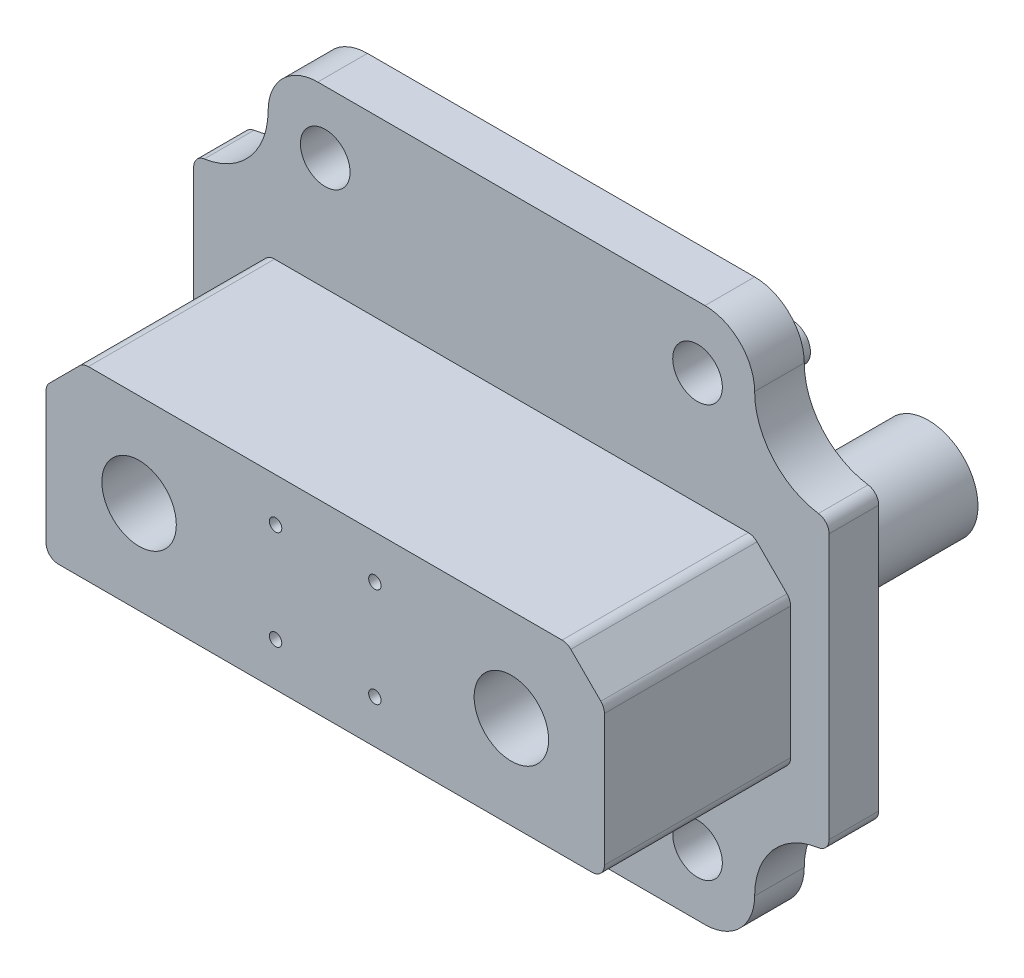
SolidWorks part; units mm, degrees
ref_plane "前视基准面" through (0, 0, 0) normal (0, 0, 1) x (1, 0, 0)
ref_plane "上视基准面" through (0, 0, 0) normal (0, 1, 0) x (1, 0, 0)
ref_plane "右视基准面" through (0, 0, 0) normal (1, 0, 0) x (0, 0, -1)
sketch "草图1" plane through (0, 0, 0) normal (0, 0, 1) x (1, 0, 0)
  line L0 (-6.4155, 0) -> (7.9227, 0) construction
  line L1 (0, -7.8725) -> (0, 7.2232) construction
  line L2 (0, 10.8) -> (-9.8, 10.8)
  line L3 (-9.8, 10.8) -> (-9.8, 5.8)
  line L4 (-9.8, 5.8) -> (-12.8, 5.8)
  line L5 (-12.8, 5.8) -> (-12.8, -5.8)
  line L6 (12.8, 5.8) -> (12.8, -5.8)
  line L7 (9.8, 5.8) -> (12.8, 5.8)
  line L8 (9.8, 10.8) -> (9.8, 5.8)
  line L9 (0, 10.8) -> (9.8, 10.8)
  line L10 (0, 7.8725) -> (0, -7.2232) construction
  line L11 (0, -10.8) -> (9.8, -10.8)
  line L12 (9.8, -10.8) -> (9.8, -5.8)
  line L13 (9.8, -5.8) -> (12.8, -5.8)
  line L14 (-9.8, -5.8) -> (-12.8, -5.8)
  line L15 (-9.8, -10.8) -> (-9.8, -5.8)
  line L16 (0, -10.8) -> (-9.8, -10.8)
  point P10 (-4.9, 10.8)
  point P23 (12.8, 0)
  point P24 (-12.8, 0)
  dimension "D1" = 25.6
  dimension "D2" = 21.6
  dimension "D3" = 3
  dimension "D4" = 5
extrude "凸台-拉伸1" add sketch "草图1" along normal blind 2
sketch "草图2" plane through (0, 0, 2) normal (0, 0, 1) x (1, 0, 0)
  line L0 (-2.5297, 0) -> (2.6546, 0) construction
  line L1 (0, 3.982) -> (0, -2.7327) construction
  circle A0 centre (-7.5, 8.3) radius 1
  circle A1 centre (7.5, 8.3) radius 1
  circle A2 centre (7.5, -8.3) radius 1
  circle A3 centre (-7.5, -8.3) radius 1
  dimension "D1" = 2
  dimension "D2" = 15
  dimension "D3" = 16.6
extrude "切除-拉伸1" cut sketch "草图2" against normal up to surface (2 mm away) up to face at (0, 0, 0)
sketch "草图3" plane through (0, 0, 2) normal (0, 0, 1) x (1, 0, 0)
  line L5 (-2.1038, 0) -> (2.4291, 0) construction
  line L6 (0, 2.0062) -> (0, -2.1363) construction
  line L7 (11.25, -3.75) -> (-11.25, -3.75)
  line L9 (-11.25, -3.75) -> (-11.25, 2.25)
  line L10 (-11.25, 2.25) -> (-9.75, 3.75)
  line L11 (-9.75, 3.75) -> (9.75, 3.75)
  line L12 (11.25, -3.75) -> (11.25, 2.25)
  line L13 (11.25, 2.25) -> (9.75, 3.75)
  point P11 (0, -3.75)
  point P14 (0, 3.75)
  dimension "D1" = 7.5
  dimension "D2" = 22.5
  dimension "D3" = 1.5
  dimension "D4" = 1.5
extrude "凸台-拉伸2" add sketch "草图3" along normal blind 7.5
sketch "草图4" plane through (0, 0, 9.5) normal (0, 0, 1) x (1, 0, 0)
  line L0 (-2.4291, 0) -> (2.4941, 0) construction
  line L1 (0, 2.158) -> (0, -2.158) construction
  circle A0 centre (-7.5, 0) radius 1.5
  circle A1 centre (-2, 2) radius 0.25
  circle A2 centre (2, 2) radius 0.25
  circle A3 centre (7.5, 0) radius 1.5
  circle A4 centre (2, -2) radius 0.25
  circle A5 centre (-2, -2) radius 0.25
  dimension "D1" = 3
  dimension "D3" = 0.5
  dimension "D2" = 15
  dimension "D4" = 4
  dimension "D5" = 4
extrude "切除-拉伸2" cut sketch "草图4" against normal up to surface (7.5 mm away) up to face at (0, 0, 2)
sketch "草图5" plane through (0, 0, 0) normal (0, 0, -1) x (-1, 0, 0)
  line L1 (-10.5, -3.75) -> (10.5, -3.75)
  line L2 (-10.5, -3.75) -> (-10.5, 3.75)
  line L3 (-10.5, 3.75) -> (10.5, 3.75)
  line L4 (10.5, -3.75) -> (10.5, 3.75)
  line L5 (-10.5, -3.75) -> (10.5, 3.75) construction
  line L6 (-10.5, 3.75) -> (10.5, -3.75) construction
  point P0 (0, 0)
  dimension "D1" = 21
  dimension "D2" = 7.5
extrude "凸台-拉伸3" add sketch "草图5" along normal blind 1.7
sketch "草图6" plane through (0, 0, -1.7) normal (0, 0, -1) x (-1, 0, 0)
  line L0 (-3.8388, 0) -> (2.8628, 0) construction
  line L1 (0, 2.223) -> (0, -1.7459) construction
  circle A0 centre (-7.5, 0) radius 2
  circle A1 centre (-2, 2) radius 0.75
  circle A2 centre (2, 2) radius 0.75
  circle A3 centre (7.5, 0) radius 2
  circle A4 centre (2, -2) radius 0.75
  circle A5 centre (-2, -2) radius 0.75
  dimension "D4" = 4
  dimension "D5" = 1.5
  dimension "D1" = 15
  dimension "D2" = 4
  dimension "D3" = 4
extrude "凸台-拉伸4" add sketch "草图6" along normal blind 5.6
fillet "圆角1" radius 2 4 edges at (-9.8, -10.8, 1) (9.8, -10.8, 1) (-9.8, 10.8, 1) (9.8, 10.8, 1)
fillet "圆角2" radius 3 4 edges at (-9.8, -5.8, 1) (9.8, -5.8, 1) (-9.8, 5.8, 1) (9.8, 5.8, 1)
fillet "圆角3" radius 1 4 edges at (-10.5, 3.75, -0.85) (-10.5, -3.75, -0.85) (10.5, -3.75, -0.85) (10.5, 3.75, -0.85)
fillet "圆角4" radius 0.5 10 edges at (11.25, 2.25, 5.75) (11.25, -3.75, 5.75) (-11.25, -3.75, 5.75) (-9.75, 3.75, 5.75) (9.75, 3.75, 5.75) (-11.25, 2.25, 5.75) (12.8, 5.8, 1) (12.8, -5.8, 1) (-12.8, -5.8, 1) (-12.8, 5.8, 1)
